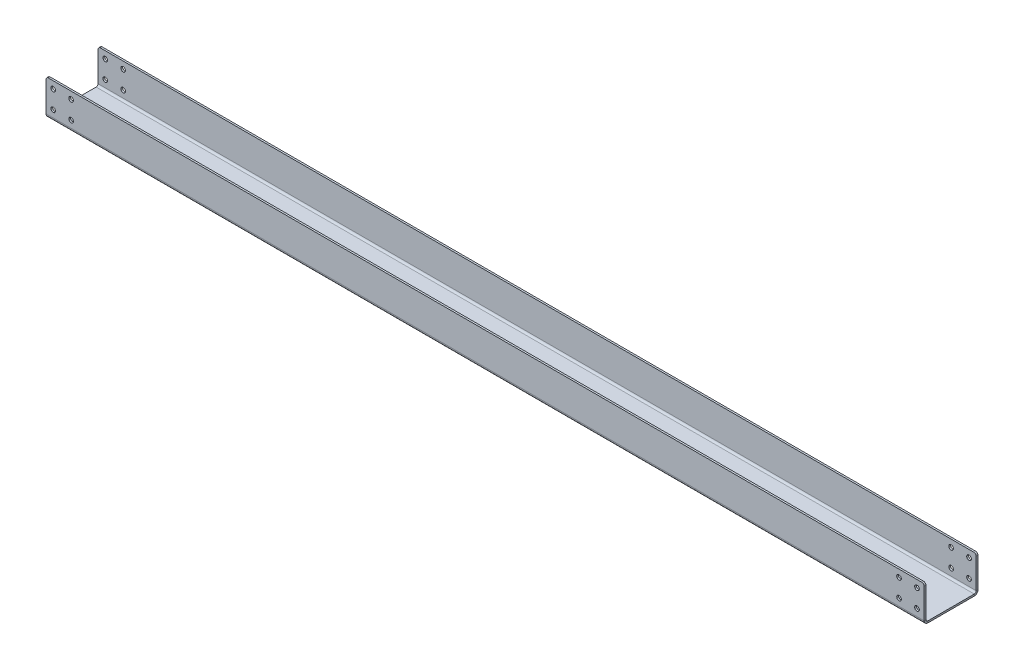
SolidWorks part; units mm, degrees
note: The reader was unsure of these and kept them because the rebuilt part matched: flange length of "Edge-Flange1", "Edge-Flange2".
ref_plane "Front Plane" through (0, 0, 0) normal (0, 0, 1) x (1, 0, 0)
ref_plane "Top Plane" through (0, 0, 0) normal (0, 1, 0) x (1, 0, 0)
ref_plane "Right Plane" through (0, 0, 0) normal (1, 0, 0) x (0, 0, -1)
sketch "Sketch1" plane through (0, 0, 0) normal (0, 1, 0) x (1, 0, 0)
  line L1 (466.09, -28.575) -> (-466.09, -28.575)
  line L2 (466.09, -28.575) -> (466.09, 28.575)
  line L3 (466.09, 28.575) -> (-466.09, 28.575)
  line L4 (-466.09, -28.575) -> (-466.09, 28.575)
  line L5 (466.09, -28.575) -> (-466.09, 28.575) construction
  line L6 (466.09, 28.575) -> (-466.09, -28.575) construction
  point P0 (0, 0)
  dimension "D1" = 932.18
  dimension "D2" = 57.15
base flange "Base-Flange1" sketch "Sketch1" thickness 1.8974 reverse thickness direction no parameters "D1"=2.032
edge flange "Edge-Flange1" sketch "Sketch8" flange angle 90 flange length 38.1 flange position material inside bend radius 2.032 thickness 1.8974 relief rectangular parameters "D6"=10
sketch "Sketch8" plane through (0, 0, 28.575) normal (0, 0, -1) x (-1, 0, 0)
  line L2 (-466.09, 0) -> (-466.09, 36.2026)
  line L3 (-466.09, 36.2026) -> (466.09, 36.2026)
  line L4 (466.09, 36.2026) -> (466.09, 0)
  line L5 (466.09, 0) -> (-466.09, 0) construction
  line L6 (466.09, 0) -> (-466.09, 0)
bend "EdgeBend1" bend radius 2.032 bend angle 90 parameters "D5"=1
edge flange "Edge-Flange2" sketch "Sketch11" flange angle 90 flange length 38.1 flange position material inside bend radius 2.032 thickness 1.8974 relief rectangular parameters "D6"=10
sketch "Sketch11" plane through (0, 0, -28.575) normal (0, 0, 1) x (1, 0, 0)
  line L2 (-466.09, 0) -> (-466.09, 36.2026)
  line L3 (-466.09, 36.2026) -> (466.09, 36.2026)
  line L4 (466.09, 36.2026) -> (466.09, 0)
  line L5 (466.09, 0) -> (-466.09, 0) construction
  line L6 (466.09, 0) -> (-466.09, 0)
bend "EdgeBend2" bend radius 2.032 bend angle 90 parameters "D5"=2
sketch "Sketch12" plane through (0, 0, 28.575) normal (0, 0, 1) x (1, 0, 0)
  line L0 (-466.09, 2.032) -> (-466.09, 36.2026) construction
  line L1 (-466.09, 36.2026) -> (466.09, 36.2026) construction
  line L2 (-466.09, 2.032) -> (466.09, 2.032) construction
  line L3 (-431.8, 2.032) -> (-469.9, 2.032) construction
  line L4 (-431.8, 2.032) -> (-431.8, 50.5557) construction
  line L5 (-431.8, 50.5557) -> (-469.9, 50.5557) construction
  line L6 (-469.9, 2.032) -> (-469.9, 50.5557) construction
  circle A0 centre (-458.47, 28.5826) radius 2.4638
  circle A1 centre (-458.47, 9.5326) radius 2.4638
  circle A2 centre (-439.42, 28.5826) radius 2.4638
  circle A3 centre (-439.42, 9.5326) radius 2.4638
  dimension "D1" = 4.9276
  dimension "D2" = 7.62
  dimension "D3" = 19.05
  dimension "D4" = 7.62
  dimension "D5" = 19.05
  dimension "D6" = 38.1
  dimension "D7" = 3.81
  dimension "D8" = 48.5237
  dimension "D9" = 15.24
extrude "Cut-Extrude1" cut sketch "Sketch12" against normal through all normal cut yes
mirror "Mirror1" about plane through (0, 0, 0) normal (1, 0, 0) of "Cut-Extrude1"
fillet "Fillet1" radius 2.54 4 edges at (-466.09, 36.2026, -27.6263) (-466.09, 36.2026, 27.6263) (466.09, 36.2026, -27.6263) (466.09, 36.2026, 27.6263)
sketch "Bend-Lines1" [suppressed] plane through (0, 0, 0) normal (0, 1, 0) x (1, 0, 0)
sketch "Bounding-Box1" [suppressed] plane through (0, 0, 0) normal (0, 1, 0) x (1, 0, 0)
sheet metal parameters "Sheet-Metal1" thickness 1.8974 parameters "D1"=2.032
flat pattern "Flat-Pattern1" [suppressed]
sketch "Bend-Lines2" plane through (0, 0, 0) normal (0, 1, 0) x (1, 0, 0)
sketch3d "Bounding-Box2" [suppressed]
  line L0 (-469.9, -28.575, 0) -> (469.9, -28.575, 0) construction
  line L1 (-469.9, 28.575, 0) -> (469.9, 28.575, 0) construction
  line L2 (-469.9, -28.575, 0) -> (-469.9, 28.575, 0) construction
  line L3 (469.9, -28.575, 0) -> (469.9, 28.575, 0) construction
sheet metal parameters "Sheet-Metal2" thickness 1.8974 parameters "D1"=2.032
flat pattern "Flat-Pattern1"
sketch "Bend-Lines2" plane through (0, 0, 0) normal (0, 1, 0) x (1, 0, 0)
  line L0 (-469.9, -26.9866) -> (469.9, -26.9866) construction
  line L1 (-469.9, -26.9866) -> (469.9, -26.9866) construction
sketch3d "Bounding-Box2" [suppressed]
  line L0 (469.9, -63.4983, 0) -> (-469.9, -63.4983, 0) construction
  line L1 (469.9, 28.575, 0) -> (-469.9, 28.575, 0) construction
  line L2 (469.9, -63.4983, 0) -> (469.9, 28.575, 0) construction
  line L3 (-469.9, -63.4983, 0) -> (-469.9, 28.575, 0) construction
bend of the flat pattern "Flatten-<EdgeBend1>1"
sheet metal parameters "Sheet-Metal3" thickness 1.8974 parameters "D1"=2.032
flat pattern "Flat-Pattern1"
sketch "Bend-Lines2" plane through (0, 0, 0) normal (0, 1, 0) x (1, 0, 0)
  line L0 (-466.09, -26.9866) -> (466.09, -26.9866) construction
  line L1 (-466.09, -26.9866) -> (466.09, -26.9866) construction
  line L2 (466.09, 26.9866) -> (-466.09, 26.9866) construction
  line L3 (466.09, 26.9866) -> (-466.09, 26.9866) construction
sketch3d "Bounding-Box2" [suppressed]
  line L0 (466.09, -63.4983, 0) -> (-466.09, -63.4983, 0) construction
  line L1 (466.09, 63.4983, 0) -> (-466.09, 63.4983, 0) construction
  line L2 (466.09, -63.4983, 0) -> (466.09, 63.4983, 0) construction
  line L3 (-466.09, -63.4983, 0) -> (-466.09, 63.4983, 0) construction
bend of the flat pattern "Flatten-<EdgeBend1>1"
bend of the flat pattern "Flatten-<EdgeBend2>1"
sheet metal parameters "Sheet-Metal4" thickness 1.8974 parameters "D1"=2.032
flat pattern "Flat-Pattern1"
sketch "Bend-Lines2" plane through (0, 0, 0) normal (0, 1, 0) x (1, 0, 0)
  line L0 (-466.09, -26.9866) -> (466.09, -26.9866) construction
  line L1 (-466.09, -26.9866) -> (466.09, -26.9866) construction
  line L2 (466.09, 26.9866) -> (-466.09, 26.9866) construction
  line L3 (466.09, 26.9866) -> (-466.09, 26.9866) construction
sketch3d "Bounding-Box2" [suppressed]
  line L0 (466.09, -63.4983, 0) -> (-466.09, -63.4983, 0) construction
  line L1 (466.09, 63.4983, 0) -> (-466.09, 63.4983, 0) construction
  line L2 (466.09, -63.4983, 0) -> (466.09, 63.4983, 0) construction
  line L3 (-466.09, -63.4983, 0) -> (-466.09, 63.4983, 0) construction
bend of the flat pattern "Flatten-<EdgeBend1>1"
bend of the flat pattern "Flatten-<EdgeBend2>1"
sheet metal parameters "Sheet-Metal5" thickness 1.8974 parameters "D1"=2.032
flat pattern "Flat-Pattern1"
sketch "Bend-Lines2" plane through (0, 0, 0) normal (0, 1, 0) x (1, 0, 0)
  line L0 (-466.09, -26.9866) -> (466.09, -26.9866) construction
  line L1 (-466.09, -26.9866) -> (466.09, -26.9866) construction
  line L2 (466.09, 26.9866) -> (-466.09, 26.9866) construction
  line L3 (466.09, 26.9866) -> (-466.09, 26.9866) construction
sketch3d "Bounding-Box2" [suppressed]
  line L0 (466.09, -63.4983, 0) -> (-466.09, -63.4983, 0) construction
  line L1 (466.09, 63.4983, 0) -> (-466.09, 63.4983, 0) construction
  line L2 (466.09, -63.4983, 0) -> (466.09, 63.4983, 0) construction
  line L3 (-466.09, -63.4983, 0) -> (-466.09, 63.4983, 0) construction
bend of the flat pattern "Flatten-<EdgeBend1>1"
bend of the flat pattern "Flatten-<EdgeBend2>1"
